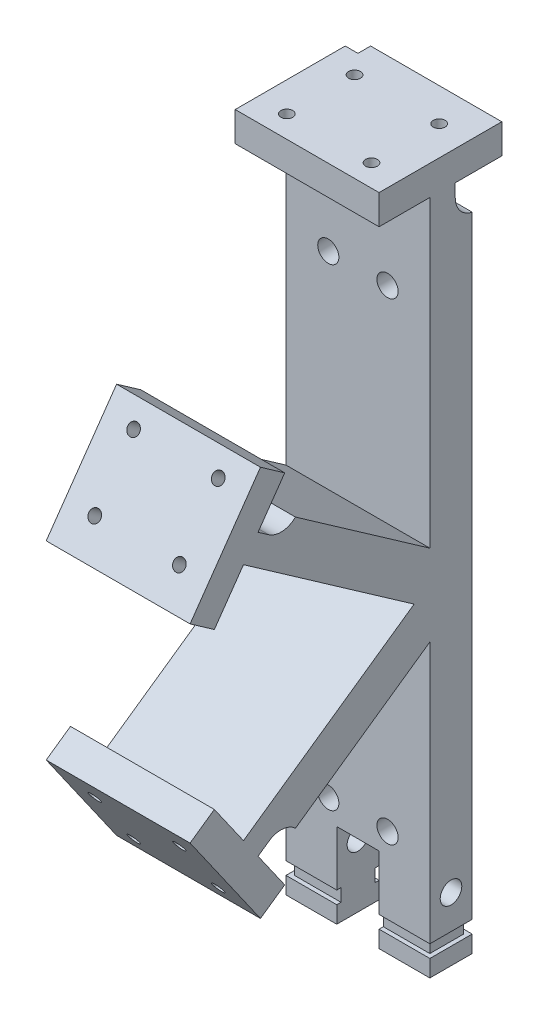
SolidWorks part; units mm, degrees
ref_plane "Front Plane" through (0, 0, 0) normal (0, 0, 1) x (1, 0, 0)
ref_plane "Top Plane" through (0, 0, 0) normal (0, 1, 0) x (1, 0, 0)
ref_plane "Right Plane" through (0, 0, 0) normal (1, 0, 0) x (0, 0, -1)
sketch "Sketch2" plane through (0, 0, 0) normal (0, 0, 1) x (1, 0, 0)
  line L1 (-73.75, 88.375) -> (73.75, 88.375)
  line L2 (-73.75, 88.375) -> (-73.75, -88.375)
  line L3 (-73.75, -88.375) -> (73.75, -88.375)
  line L4 (73.75, 88.375) -> (73.75, -88.375)
  line L5 (-73.75, 88.375) -> (73.75, -88.375) construction
  line L6 (-73.75, -88.375) -> (73.75, 88.375) construction
  point P0 (0, 0)
  dimension "D1" = 147.5
  dimension "D2" = 176.75
extrude "Boss-Extrude1" add sketch "Sketch2" along normal blind 10
sketch "Sketch3" plane through (-73.75, 0, 0) normal (-1, 0, 0) x (0, 0, 1)
  line L0 (0, 88.375) -> (0, -88.375) construction
  line L1 (-7, 88.375) -> (22, 88.375)
  line L2 (-7, 88.375) -> (-7, 73.375)
  line L3 (-7, 73.375) -> (22, 73.375)
  line L4 (22, 88.375) -> (22, 73.375)
  line L5 (10, 88.375) -> (10, -88.375) construction
  line L6 (0, 0) -> (56.8374, 0) construction
  line L7 (22, -88.375) -> (22, -73.375)
  line L8 (-7, -88.375) -> (-7, -73.375)
  line L9 (-7, -88.375) -> (22, -88.375)
  line L10 (-7, -73.375) -> (22, -73.375)
  line L11 (10, 88.375) -> (0, 88.375) construction
  dimension "D1" = 7
  dimension "D2" = 12
  dimension "D3" = 15
  dimension "D4" = 0
extrude "Boss-Extrude2" add sketch "Sketch3" against normal blind 34
ref_plane "Plane1" through (0, 0, 0) normal (1, 0, 0) x (0, 0, -1)
mirror "Mirror1" about plane through (0, 0, 0) normal (1, 0, 0) of "Boss-Extrude2"
sketch "Sketch5" plane through (-73.75, 0, 0) normal (-1, 0, 0) x (0, 0, 1)
  line L0 (10, 73.375) -> (10, -73.375) construction
  line L1 (-35, 0) -> (-35, 43.6802) construction
  line L2 (0, 0) -> (0, 73.375) construction
  line L3 (0, 0) -> (10, 0)
  line L4 (-35, 0) -> (0, 0) construction
  line L5 (-7, 88.375) -> (22, 88.375)
  line L6 (-7, 88.375) -> (-7, 73.375)
  line L7 (-7, 73.375) -> (22, 73.375)
  line L8 (22, 88.375) -> (22, 73.375)
  line L9 (0, 73.375) -> (10, 73.375)
  line L10 (0, 73.375) -> (0, 0)
  line L11 (0, 0) -> (10, 0)
  line L12 (10, 73.375) -> (10, 0)
  line L13 (5, 0) -> (5, -4.9122)
  line L18 (58.2224, 51.916) -> (50.0308, 46.1802)
  line L19 (-7, 73.375) -> (22, 73.375)
  line L20 (-7, 73.375) -> (-7, 63.375)
  line L21 (-7, 63.375) -> (22, 63.375)
  line L22 (22, 73.375) -> (22, 63.375)
  line L23 (50.0308, 46.1802) -> (66.6646, 22.4248)
  line L24 (58.2224, 51.916) -> (74.8561, 28.1606)
  line L25 (74.8561, 28.1606) -> (66.6646, 22.4248)
  line L26 (67.9732, 37.9904) -> (7.8679, -4.0958)
  line L27 (62.2374, 46.1819) -> (2.1321, 4.0958)
  line L28 (2.1321, 4.0958) -> (7.8679, -4.0958)
  line L29 (2.1321, -4.0958) -> (7.8679, 4.0958)
  line L30 (62.2374, -46.1819) -> (2.1321, -4.0958)
  line L31 (67.9732, -37.9904) -> (7.8679, 4.0958)
  line L32 (5, 0) -> (5, 4.9122)
  line L33 (74.8561, -28.1606) -> (66.6646, -22.4248)
  line L34 (58.2224, -51.916) -> (74.8561, -28.1606)
  line L35 (50.0308, -46.1802) -> (66.6646, -22.4248)
  line L36 (58.2224, -51.916) -> (50.0308, -46.1802)
  line L37 (50.0308, 46.1802) -> (66.6646, 22.4248)
  line L38 (-7, 63.375) -> (22, 63.375)
  line L39 (-7, 63.375) -> (-7, 48.375)
  line L40 (-7, 48.375) -> (22, 48.375)
  line L41 (22, 63.375) -> (22, 48.375)
  line L42 (50.0308, 46.1802) -> (37.7436, 37.5766)
  line L43 (37.7436, 37.5766) -> (54.3773, 13.8212)
  line L44 (66.6646, 22.4248) -> (54.3773, 13.8212)
  line L45 (50.0308, -46.1802) -> (66.6646, -22.4248)
  line L46 (66.6646, -22.4248) -> (54.3773, -13.8212)
  line L47 (50.0308, -46.1802) -> (37.7436, -37.5766)
  line L48 (37.7436, -37.5766) -> (54.3773, -13.8212)
  circle A0 centre (-35, 0) radius 110
  point P17 (-35, 0)
  point P31 (5, 0)
  point P34 (5, 0)
  point P51 (5, 0)
  line M9 (10, -73.375) -> (10, 73.375)
  dimension "D3" = 10
  dimension "D1" = 220
  dimension "D2" = 35
  dimension "D5" = 15
  dimension "D4" = 2
  dimension "D6" = 2
extrude "Boss-Extrude3" add sketch "Sketch5" against normal blind 34 contours L31 L26 L23 L27 L12 | L30 L35 L31 L26 M9 | L26 L31 M9 | L44 L23 L26 L43 | L27 L43 L26 L23 | L42 L43 L27 L23 | L48 L47 L35 L30 | L48 L30 L35 L31 | L48 L31 L35 L46 region at (-73.75, 0, 11.2391) region at (-73.75, 15.8458, 27.7303) region at (-73.75, -15.8458, 27.7303) region at (-73.75, 39.0114, 45.8947) region at (-73.75, 32.0486, 50.7701) region at (-73.75, -32.0486, 50.7701) region at (-73.75, -39.0114, 45.8947) region at (-73.75, 23.0379, 57.0795) region at (-73.75, -23.0379, 57.0795)
sketch "Sketch8" plane through (0, 0, 22) normal (0, 0, 1) x (1, 0, 0)
  line L1 (73.75, 88.375) -> (-39.75, 88.375)
  line L2 (73.75, 88.375) -> (73.75, -88.375)
  line L3 (73.75, -88.375) -> (-39.75, -88.375)
  line L4 (-39.75, 88.375) -> (-39.75, -88.375)
extrude "Cut-Extrude1" cut sketch "Sketch8" against normal blind 30
sketch "Sketch9" plane through (0, 0, 0) normal (0, 0, -1) x (-1, 0, 0)
  line L0 (39.75, 73.375) -> (39.75, -73.375) construction
  line L4 (39.75, 73.375) -> (73.75, 73.375) construction
  line L6 (0, 0) -> (126.3955, 0) construction
  line L8 (39.75, -73.375) -> (73.75, -73.375) construction
  circle A0 centre (49.75, 58.375) radius 2.5
  circle A2 centre (63.75, 58.375) radius 2.5
  circle A5 centre (49.75, -53.375) radius 2.5
  circle A6 centre (63.75, -53.375) radius 2.5
  dimension "D1" = 5
  dimension "D2" = 14
  dimension "D3" = 10
  dimension "D4" = 15
  dimension "D6" = 5
  dimension "D7" = 20
  dimension "D8" = 10
  dimension "D5" = 2
  dimension "D9" = 2
extrude "Cut-Extrude2" cut sketch "Sketch9" against normal through all
sketch "Sketch10" plane through (0, 0, -7) normal (0, 0, -1) x (-1, 0, 0)
  line L1 (73.75, 88.375) -> (70.75, 88.375)
  line L2 (73.75, 88.375) -> (73.75, 85.375)
  line L3 (73.75, 85.375) -> (70.75, 85.375)
  line L4 (70.75, 88.375) -> (70.75, 85.375)
  dimension "D1" = 3
  dimension "D2" = 3
extrude "Cut-Extrude3" cut sketch "Sketch10" against normal blind 3
sketch "Sketch11" plane through (0, 0, 0) normal (0, 0, -1) x (-1, 0, 0)
  line L0 (39.75, 73.375) -> (39.75, -73.375) construction
  line L1 (39.75, -61.375) -> (73.75, -61.375)
  line L2 (39.75, -61.375) -> (39.75, -73.375)
  line L3 (39.75, -73.375) -> (73.75, -73.375)
  line L4 (73.75, -61.375) -> (73.75, -73.375)
  line L5 (39.75, -65.375) -> (73.75, -65.375)
  line L7 (39.75, -61.375) -> (42.75, -61.375)
  line L8 (39.75, -61.375) -> (39.75, -73.375)
  line L9 (39.75, -73.375) -> (42.75, -73.375)
  line L10 (42.75, -61.375) -> (42.75, -73.375)
  line L11 (73.75, -61.375) -> (70.75, -61.375)
  line L12 (73.75, -61.375) -> (73.75, -73.375)
  line L13 (73.75, -73.375) -> (70.75, -73.375)
  line L14 (70.75, -61.375) -> (70.75, -73.375)
  line L15 (51.75, -65.375) -> (61.75, -65.375)
  line L16 (51.75, -65.375) -> (51.75, -73.375)
  line L17 (51.75, -73.375) -> (61.75, -73.375)
  line L18 (61.75, -65.375) -> (61.75, -73.375)
  line L19 (73.75, -73.375) -> (39.75, -73.375)
  line L20 (73.75, -73.375) -> (73.75, -58.375)
  line L21 (73.75, -58.375) -> (39.75, -58.375)
  line L22 (39.75, -73.375) -> (39.75, -58.375)
  line L23 (39.75, -73.375) -> (73.75, -73.375)
  line L24 (39.75, -73.375) -> (39.75, -88.375)
  line L25 (39.75, -88.375) -> (73.75, -88.375)
  line L26 (73.75, -73.375) -> (73.75, -88.375)
  line L27 (61.75, -73.375) -> (51.75, -73.375)
  line L28 (61.75, -73.375) -> (61.75, -58.375)
  line L30 (51.75, -73.375) -> (51.75, -58.375)
  line M17 (39.75, -73.375) -> (73.75, -73.375)
  dimension "D1" = 12
  dimension "D2" = 4
  dimension "D3" = 3
  dimension "D4" = 3
  dimension "D5" = 10
  dimension "D6" = 9
  dimension "D7" = 15
extrude "Cut-Extrude8" cut sketch "Sketch11" against normal blind 40 and the other way blind 40 contours L30 L5 L28 L1 | L18 L5 L16 M17 | L30 L1 L28 L21 | L26 L3 L24 L25 M17 region at (-56.75, -59.875, 0) region at (-56.75, -63.375, 0) region at (-56.75, -80.875, 0) region at (-56.75, -69.375, 0)
sketch "Sketch14" plane through (-73.75, 0, 0) normal (-1, 0, 0) x (0, 0, 1)
  line L0 (10, -9.6049) -> (10, -73.375) construction
  line L1 (0, -73.375) -> (10, -73.375) construction
  circle A0 centre (5, -63.375) radius 2.55
  dimension "D1" = 5
  dimension "D2" = 10
  dimension "D3" = 5.1
extrude "Cut-Extrude9" cut sketch "Sketch14" against normal blind 40
sketch "Sketch15" plane through (0, 88.375, 0) normal (0, 1, 0) x (1, 0, 0)
  line L0 (-39.75, -22) -> (-39.75, 7) construction
  line L1 (-39.75, -22) -> (-73.75, -22) construction
  circle A0 centre (-46.75, -16.8) radius 1.4
  circle A2 centre (-66.75, -16.8) radius 1.4
  circle A3 centre (-66.75, -0.8) radius 1.4
  circle A4 centre (-46.75, -0.8) radius 1.4
  dimension "D1" = 2.8
  dimension "D2" = 7
  dimension "D3" = 5.2
  dimension "D4" = 2
  dimension "D5" = 2
extrude "Cut-Extrude10" cut sketch "Sketch15" against normal blind 10 and the other way through all
sketch "Sketch16" plane through (-73.75, 0, 0) normal (-1, 0, 0) x (0, 0, 1)
  line L1 (0, 73.375) -> (-7, 73.375)
  line L6 (10, 73.375) -> (22, 73.375)
  line L10 (22, 73.375) -> (22, 88.375) construction
  line L19 (-7, 73.375) -> (4, 73.375)
  line L20 (-7, 73.375) -> (-7, 81.375)
  line L21 (-7, 81.375) -> (4, 81.375)
  line L22 (4, 73.375) -> (4, 81.375)
  line L23 (10, 73.375) -> (22, 73.375)
  line L24 (10, 73.375) -> (10, 81.375)
  line L25 (10, 81.375) -> (22, 81.375)
  line L26 (22, 73.375) -> (22, 81.375)
  line L27 (0, 0) -> (0, 73.375) construction
  line L28 (0, 73.375) -> (-7, 73.375)
  line L31 (-7, 73.375) -> (-7, 79.375)
  line L32 (0, 0) -> (10, 0) construction
  line L33 (5, 0) -> (5, 71.2995) construction
  line M29 (10, 73.375) -> (22, 73.375)
  line M30 (22, 73.375) -> (22, 88.375)
  line M34 (-7, 85.375) -> (-7, 73.375)
  line M35 (-7, 73.375) -> (0, 73.375)
  dimension "D1" = 8
  dimension "D2" = 8
  dimension "D3" = 11
extrude "Cut-Extrude11" cut sketch "Sketch16" against normal through all contours L19 L22 L21 L20 M34 M35 | L25 L24 M29 M30 region at (-73.75, 77.375, -1.5) region at (-73.75, 77.375, 16)
fillet "Fillet1" radius 5 1 edges at (-56.75, 73.375, 4)
sketch "Sketch17" plane through (0, 38.6996, 55.2688) normal (0, 0.5736, 0.8192) x (1, 0, 0)
  line L0 (-39.75, 9.1321) -> (-73.75, 9.1321) construction
  line L1 (-73.75, 9.1321) -> (-73.75, -19.8679) construction
  circle A0 centre (-66.75, 3.9321) radius 1.4
  circle A1 centre (-46.75, 3.9321) radius 1.4
  circle A2 centre (-46.75, -12.0679) radius 1.4
  circle A3 centre (-66.75, -12.0679) radius 1.4
  dimension "D1" = 5.2
  dimension "D2" = 7
  dimension "D3" = 2
  dimension "D4" = 2
extrude "Cut-Extrude12" cut sketch "Sketch17" against normal blind 10
sketch "Sketch18" plane through (0, -38.6996, 55.2688) normal (0, -0.5736, 0.8192) x (1, 0, 0)
  line L0 (-39.75, -9.1321) -> (-39.75, 19.8679) construction
  line L1 (-39.75, -9.1321) -> (-73.75, -9.1321) construction
  circle A0 centre (-46.75, -3.9321) radius 1.4
  circle A1 centre (-66.75, -3.9321) radius 1.4
  circle A2 centre (-66.75, 12.0679) radius 1.4
  circle A3 centre (-46.75, 12.0679) radius 1.4
  dimension "D1" = 7
  dimension "D2" = 5.2
  dimension "D3" = 2
  dimension "D4" = 2
extrude "Cut-Extrude13" cut sketch "Sketch18" against normal blind 10
sketch "Sketch20" plane through (-73.75, 0, 0) normal (-1, 0, 0) x (0, 0, 1)
  line L0 (37.7436, 37.5766) -> (41.7586, 31.8425)
  line L1 (41.7586, 31.8425) -> (44.0529, 28.5659)
  line L2 (37.7436, 37.5766) -> (44.2968, 42.1652)
  line L3 (50.0308, 46.1802) -> (37.7436, 37.5766) construction
  line L4 (44.2968, 42.1652) -> (50.6061, 33.1545)
  line L5 (50.6061, 33.1545) -> (44.0529, 28.5659)
  line L6 (47.4944, 23.651) -> (54.3773, 13.8212)
  line L7 (54.3773, 13.8212) -> (60.9305, 18.4098)
  line L8 (66.6646, 22.4248) -> (54.3773, 13.8212) construction
  line L9 (60.9305, 18.4098) -> (54.0476, 28.2396)
  line L10 (54.0476, 28.2396) -> (47.4944, 23.651)
  line L11 (13.7172, 0) -> (31.504, 0) construction
  line L12 (54.0476, -28.2396) -> (47.4944, -23.651)
  line L13 (60.9305, -18.4098) -> (54.0476, -28.2396)
  line L14 (54.3773, -13.8212) -> (60.9305, -18.4098)
  line L15 (47.4944, -23.651) -> (54.3773, -13.8212)
  line L16 (50.6061, -33.1545) -> (44.0529, -28.5659)
  line L17 (44.2968, -42.1652) -> (50.6061, -33.1545)
  line L18 (37.7436, -37.5766) -> (44.2968, -42.1652)
  line L19 (41.7586, -31.8425) -> (44.0529, -28.5659)
  line L20 (37.7436, -37.5766) -> (41.7586, -31.8425)
  dimension "D1" = 4
  dimension "D2" = 8
  dimension "D3" = 11
  dimension "D4" = 8
  dimension "D5" = 12
extrude "Cut-Extrude14" cut sketch "Sketch20" against normal blind 34
fillet "Fillet2" radius 5 2 edges at (-56.75, -28.5659, 44.0529) (-56.75, 28.5659, 44.0529)
sketch "Sketch21" plane through (0, -73.375, 0) normal (0, -1, 0) x (1, 0, 0)
  line L1 (-73.75, 10) -> (-61.75, 10)
  line L2 (-73.75, 10) -> (-73.75, 0)
  line L3 (-73.75, 0) -> (-61.75, 0)
  line L4 (-61.75, 10) -> (-61.75, 0)
  line L5 (-51.75, 10) -> (-39.75, 10)
  line L6 (-51.75, 10) -> (-51.75, 0)
  line L7 (-51.75, 0) -> (-39.75, 0)
  line L8 (-39.75, 10) -> (-39.75, 0)
extrude "Boss-Extrude4" add sketch "Sketch21" along normal blind 5
sketch "Sketch22" plane through (-73.75, 0, 0) normal (-1, 0, 0) x (0, 0, 1)
  line L0 (0, 73.375) -> (0, -78.375) construction
  line L1 (0, -71.375) -> (10, -71.375)
  line L2 (0, -71.375) -> (0, -74.375)
  line L3 (0, -74.375) -> (10, -74.375)
  line L4 (10, -71.375) -> (10, -74.375)
  line L5 (10, -9.6049) -> (10, -78.375) construction
  line L6 (10, -78.375) -> (0, -78.375) construction
  dimension "D1" = 4
  dimension "D2" = 3
extrude "Cut-Extrude15" cut sketch "Sketch22" against normal blind 1
ref_plane "Plane2" through (-56.75, 0, 0) normal (-1, 0, 0) x (0, 0, 1)
mirror "Mirror2" about plane through (-56.75, 0, 0) normal (-1, 0, 0) of "Cut-Extrude15"
sketch "Sketch23" plane through (0, 0, 0) normal (0, 0, -1) x (-1, 0, 0)
  line L0 (61.75, -78.375) -> (61.75, -58.375) construction
  line L1 (72.75, -71.375) -> (61.75, -71.375)
  line L2 (72.75, -71.375) -> (72.75, -74.375)
  line L3 (72.75, -74.375) -> (61.75, -74.375)
  line L4 (61.75, -71.375) -> (61.75, -74.375)
  line L5 (51.75, -78.375) -> (51.75, -58.375) construction
  line L6 (40.75, -74.375) -> (51.75, -74.375)
  line L7 (40.75, -74.375) -> (40.75, -71.375)
  line L8 (40.75, -71.375) -> (51.75, -71.375)
  line L9 (51.75, -74.375) -> (51.75, -71.375)
extrude "Cut-Extrude16" cut sketch "Sketch23" against normal blind 1
sketch "Sketch24" plane through (0, 0, 10) normal (0, 0, 1) x (1, 0, 0)
  line L1 (-72.75, -71.375) -> (-40.75, -71.375)
  line L2 (-72.75, -71.375) -> (-72.75, -74.375)
  line L3 (-72.75, -74.375) -> (-40.75, -74.375)
  line L4 (-40.75, -71.375) -> (-40.75, -74.375)
extrude "Cut-Extrude17" cut sketch "Sketch24" against normal blind 1
